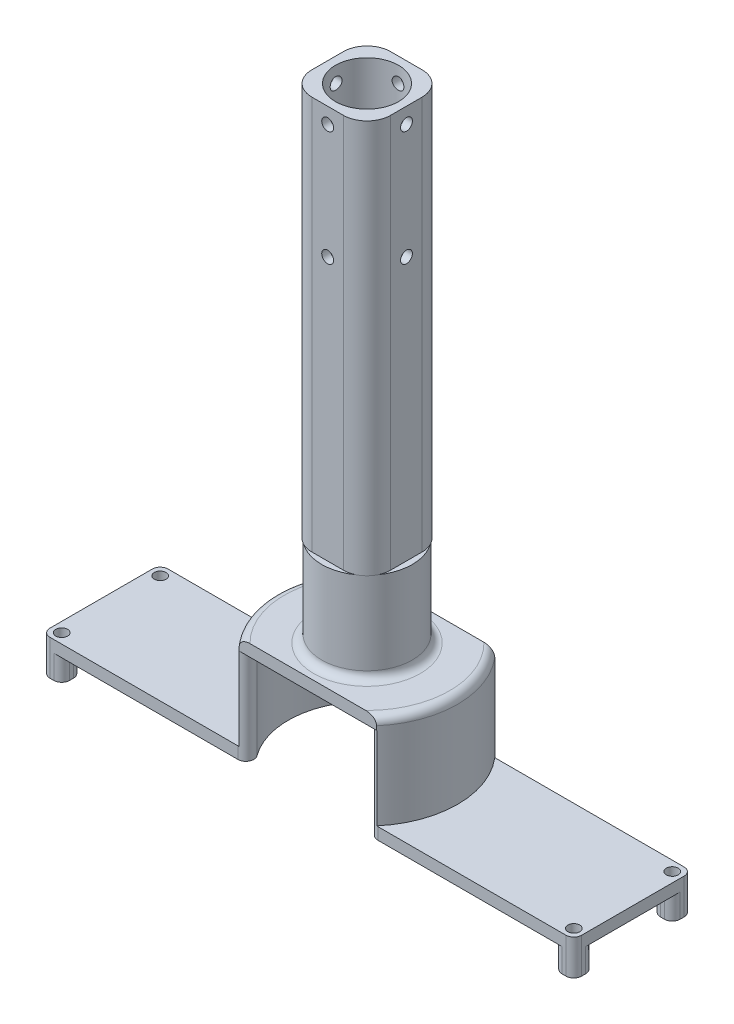
SolidWorks part; units mm, degrees
ref_plane "前视基准面" through (0, 0, 0) normal (0, 0, 1) x (1, 0, 0)
ref_plane "上视基准面" through (0, 0, 0) normal (0, 1, 0) x (1, 0, 0)
ref_plane "右视基准面" through (0, 0, 0) normal (1, 0, 0) x (0, 0, -1)
sketch "草图1" plane through (0, 0, 0) normal (0, 1, 0) x (1, 0, 0)
  line L1 (-90.0247, 40.7512) -> (44.9753, 40.7512)
  line L2 (-90.0247, 40.7512) -> (-90.0247, 10.7512)
  line L3 (-90.0247, 10.7512) -> (44.9753, 10.7512)
  line L4 (44.9753, 40.7512) -> (44.9753, 10.7512)
  circle A0 centre (-87.5247, 38.2512) radius 1.5
  circle A1 centre (-87.5247, 13.2512) radius 1.5
  circle A2 centre (42.4753, 13.2512) radius 1.5
  circle A3 centre (42.4753, 38.2512) radius 1.5
  circle A4 centre (-22.5247, 25.7512) radius 20
  dimension "D1" = 25
  dimension "D4" = 130
  dimension "D5" = 25
  dimension "D6" = 130
  dimension "D7" = 2.5
  dimension "D8" = 2.5
  dimension "D9" = 67.5
  dimension "D10" = 15
  dimension "D11" = 3
  dimension "D12" = 3
  dimension "D13" = 3
  dimension "D14" = 3
  dimension "D2" = 30
  dimension "D3" = 135
extrude "凸台-拉伸1" add sketch "草图1" along normal blind 3 contours A4 L1 L2 L3 A1 A0 | A4 L3 L4 L1 A2 A3 region at (-64.983, 0, -25.7512) region at (19.9336, 0, -25.7512)
sketch "草图2" plane through (0, 0, 0) normal (0, -1, 0) x (1, 0, 0)
  line L1 (-90.0247, -10.7512) -> (-85.0247, -10.7512)
  line L2 (-90.0247, -10.7512) -> (-90.0247, -15.7512)
  line L3 (-90.0247, -15.7512) -> (-85.0247, -15.7512)
  line L4 (-85.0247, -10.7512) -> (-85.0247, -15.7512)
  line L5 (44.9753, -10.7512) -> (39.9753, -10.7512)
  line L6 (44.9753, -10.7512) -> (44.9753, -15.7512)
  line L7 (44.9753, -15.7512) -> (39.9753, -15.7512)
  line L8 (39.9753, -10.7512) -> (39.9753, -15.7512)
  line L9 (44.9753, -40.7512) -> (39.9753, -40.7512)
  line L10 (44.9753, -40.7512) -> (44.9753, -35.7512)
  line L11 (44.9753, -35.7512) -> (39.9753, -35.7512)
  line L12 (39.9753, -40.7512) -> (39.9753, -35.7512)
  line L13 (-90.0247, -40.7512) -> (-85.0247, -40.7512)
  line L14 (-90.0247, -40.7512) -> (-90.0247, -35.7512)
  line L15 (-90.0247, -35.7512) -> (-85.0247, -35.7512)
  line L16 (-85.0247, -40.7512) -> (-85.0247, -35.7512)
  circle A0 centre (-87.5247, -38.2512) radius 1.5
  circle A1 centre (-87.5247, -13.2512) radius 1.5
  circle A2 centre (42.4753, -13.2512) radius 1.5
  circle A3 centre (42.4753, -38.2512) radius 1.5
  dimension "D1" = 5
  dimension "D3" = 3
  dimension "D2" = 5
extrude "凸台-拉伸2" add sketch "草图2" along normal blind 6
sketch "草图3" plane through (0, 3, 0) normal (0, 1, 0) x (1, 0, 0)
  line L0 (-39.9603, 40.7512) -> (-35.7535, 40.7512)
  line L1 (-90.0247, 40.7512) -> (-35.7535, 40.7512) construction
  line L2 (-5.0891, 40.7512) -> (-9.296, 40.7512)
  line L3 (-39.9603, 10.7512) -> (-35.7535, 10.7512)
  line L4 (-90.0247, 10.7512) -> (-35.7535, 10.7512) construction
  line L5 (-9.296, 10.7512) -> (-5.0891, 10.7512)
  line L6 (-9.296, 10.7512) -> (44.9753, 10.7512) construction
  arc A0 (-5.0891, 10.7512) -> (-5.0891, 40.7512) centre (-22.5247, 25.7512) ccw
  arc A1 (-9.296, 10.7512) -> (-9.296, 40.7512) centre (-22.5247, 25.7512) ccw
  arc A2 (-35.7535, 40.7512) -> (-35.7535, 10.7512) centre (-22.5247, 25.7512) ccw
  arc A3 (-39.9603, 40.7512) -> (-39.9603, 10.7512) centre (-22.5247, 25.7512) ccw
  dimension "D1" = 23
extrude "凸台-拉伸3" add sketch "草图3" along normal blind 21
sketch "草图4" plane through (0, 24, 0) normal (0, 1, 0) x (1, 0, 0)
  line L0 (-39.9603, 40.7512) -> (-5.0891, 40.7512)
  line L1 (-39.9603, 10.7512) -> (-5.0891, 10.7512)
  arc A0 (-39.9603, 40.7512) -> (-39.9603, 10.7512) centre (-22.5247, 25.7512) ccw
  circle A1 centre (-22.5247, 25.7512) radius 9.1924
  arc A2 (-5.0891, 10.7512) -> (-5.0891, 40.7512) centre (-22.5247, 25.7512) ccw
  dimension "D1" = 18.3848
extrude "凸台-拉伸4" add sketch "草图4" along normal blind 3
sketch "草图5" plane through (0, 27, 0) normal (0, 1, 0) x (1, 0, 0)
  line L1 (-13.0247, 16.2512) -> (-32.0247, 16.2512)
  line L2 (-13.0247, 16.2512) -> (-13.0247, 35.2512)
  line L3 (-13.0247, 35.2512) -> (-32.0247, 35.2512)
  line L4 (-32.0247, 16.2512) -> (-32.0247, 35.2512)
  line L5 (-11.0247, 14.2512) -> (-34.0247, 14.2512)
  line L6 (-11.0247, 14.2512) -> (-11.0247, 37.2512)
  line L7 (-11.0247, 37.2512) -> (-34.0247, 37.2512)
  line L8 (-34.0247, 14.2512) -> (-34.0247, 37.2512)
  circle A0 centre (-22.5247, 25.7512) radius 9.1924 construction
  dimension "D2" = 9.5
  dimension "D3" = 9.5
  dimension "D1" = 19
  dimension "D4" = 23
  dimension "D5" = 11.5
  dimension "D6" = 11.5
sketch "草图6" plane through (0, 27, 0) normal (0, 1, 0) x (1, 0, 0)
  circle A0 centre (-22.5247, 25.7512) radius 9.5
  circle A1 centre (-22.5247, 25.7512) radius 11.5
  dimension "D1" = 23
  dimension "D2" = 19
extrude "凸台-拉伸6" add sketch "草图6" along normal blind 23
sketch "草图7" plane through (0, 50, 0) normal (0, 1, 0) x (1, 0, 0)
  line L5 (-32.5247, 35.7512) -> (-12.5247, 35.7512)
  line L6 (-32.5247, 35.7512) -> (-32.5247, 15.7512)
  line L7 (-32.5247, 15.7512) -> (-12.5247, 15.7512)
  line L8 (-12.5247, 35.7512) -> (-12.5247, 15.7512)
  circle A0 centre (-22.5247, 25.7512) radius 8
  dimension "D1" = 16
  dimension "D2" = 10
  dimension "D3" = 10
  dimension "D4" = 20
extrude "凸台-拉伸7" add sketch "草图7" along normal blind 100
fillet "圆角1" radius 6 4 edges at (-32.5247, 100, -35.7512) (-12.5247, 100, -35.7512) (-12.5247, 100, -15.7512) (-32.5247, 100, -15.7512)
sketch "草图8" plane through (0, 0, -15.7512) normal (0, 0, 1) x (1, 0, 0)
  line L0 (-26.5247, 150) -> (-18.5247, 150) construction
  circle A0 centre (-22.5162, 146) radius 1.5
  circle A1 centre (-22.5162, 116.86) radius 1.5
  dimension "D1" = 3
  dimension "D2" = 3
  dimension "D3" = 29.14
  dimension "D4" = 0
  dimension "D5" = 4
extrude "切除-拉伸1" cut sketch "草图8" against normal blind 100
sketch "草图9" plane through (-12.5247, 0, 0) normal (1, 0, 0) x (0, 0, -1)
  line L0 (21.7512, 150) -> (29.7512, 150) construction
  circle A0 centre (25.7734, 146) radius 1.5
  circle A1 centre (25.7734, 116.86) radius 1.5
  dimension "D1" = 29.14
  dimension "D2" = 3
  dimension "D3" = 3
  dimension "D4" = 4
extrude "切除-拉伸2" cut sketch "草图9" against normal blind 100
fillet "圆角3" radius 2 4 edges at (-45.5247, 27, -25.7512) (0.4753, 27, -25.7512) (-22.5247, 27, -14.2512) (-22.5247, 24, -16.5588)
fillet "圆角4" radius 2 16 edges at (39.9753, -3, -40.7512) (39.9753, -3, -35.7512) (39.9753, -3, -15.7512) (39.9753, -3, -10.7512) (44.9753, -1.5, -40.7512) (44.9753, -3, -35.7512) (44.9753, -3, -15.7512) (44.9753, -1.5, -10.7512) (-85.0247, -3, -10.7512) (-85.0247, -3, -15.7512) (-90.0247, -3, -15.7512) (-90.0247, -3, -35.7512) (-85.0247, -3, -40.7512) (-85.0247, -3, -35.7512) (-90.0247, -1.5, -40.7512) (-90.0247, -1.5, -10.7512)
fillet "圆角5" radius 2 4 edges at (-35.7535, 12, -40.7512) (-35.7535, 12, -10.7512) (-9.296, 12, -10.7512) (-9.296, 12, -40.7512)
fillet "圆角6" radius 2 1 edges at (-22.5247, 50, -17.7512)
